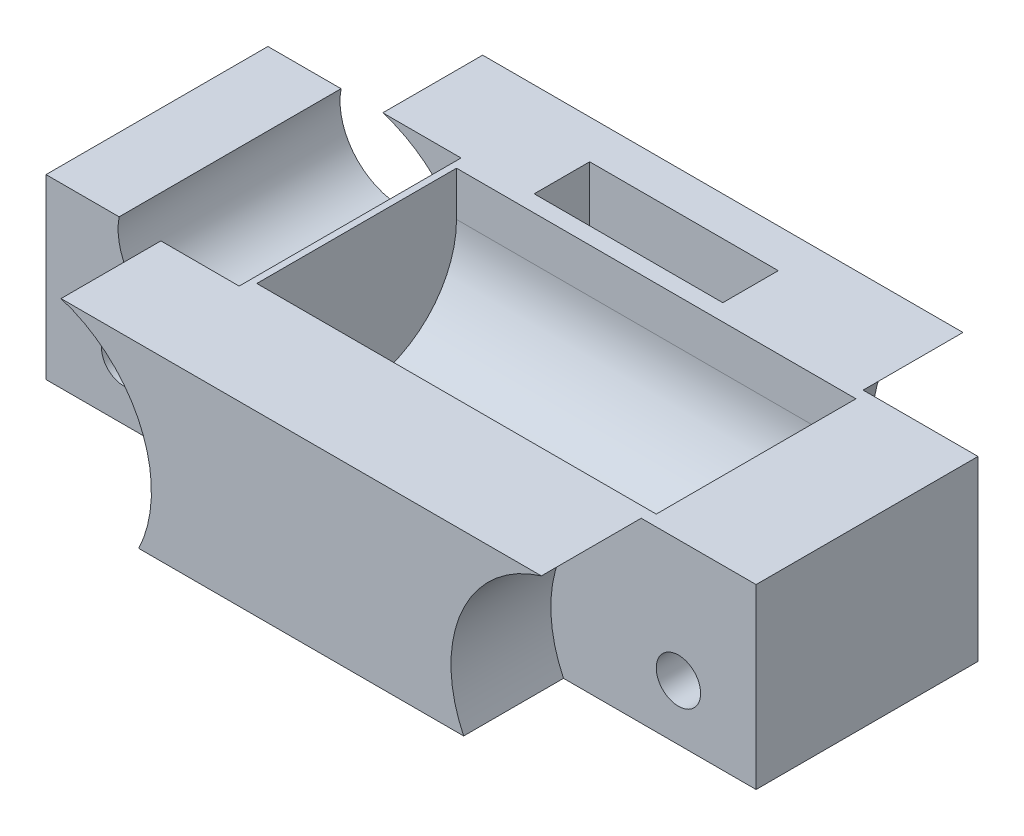
SolidWorks part; units mm, degrees
ref_plane "Front Plane" through (0, 0, 0) normal (0, 0, 1) x (1, 0, 0)
ref_plane "Top Plane" through (0, 0, 0) normal (0, 1, 0) x (1, 0, 0)
ref_plane "Right Plane" through (0, 0, 0) normal (1, 0, 0) x (0, 0, -1)
sketch "Sketch1" plane through (0, 0, 0) normal (0, 1, 0) x (1, 0, 0)
  line L1 (-32, 19) -> (32, 19)
  line L2 (-32, 19) -> (-32, -19)
  line L3 (-32, -19) -> (32, -19)
  line L4 (32, 19) -> (32, -19)
  line L5 (-32, 19) -> (32, -19) construction
  line L6 (-32, -19) -> (32, 19) construction
  point P0 (0, 0)
  dimension "D1" = 64
  dimension "D2" = 38
extrude "Boss-Extrude1" add sketch "Sketch1" along normal blind 16
sketch "Sketch2" plane through (0, 0, 0) normal (0, 0, 1) x (1, 0, 0)
  point P0 (-25, 5)
  point P1 (25, 5)
  dimension "D1" = 50
  dimension "D2" = 25
  dimension "D3" = 5
sketch "Sketch3" plane through (0, 0, 0) normal (0, 0, 1) x (1, 0, 0)
  line L0 (25, 16.5) -> (36.5, 16.5)
  line L1 (36.5, 16.5) -> (36.5, 5)
  line L2 (36.5, 5) -> (36.5, -6.5)
  line L3 (36.5, -6.5) -> (25, -6.5)
  line L4 (-25, -6.5) -> (-36.5, -6.5)
  line L5 (-36.5, -6.5) -> (-36.5, 16.5)
  line L6 (-36.5, 16.5) -> (-25, 16.5)
  circle A0 centre (-25, 5) radius 11.5
  circle A1 centre (25, 5) radius 11.5
  dimension "D1" = 23
extrude "Cut-Extrude2" cut sketch "Sketch3" along normal blind 10 from offset 10 contours A1 L3 L2 | A1 | A1 L1 L0 | A0 | A0 L5 L4 | A0 L6 L5 region at (33.9313, 13.9313, 0) region at (25, 5, 0) region at (33.9313, -3.9313, 0) region at (-25, 5, 0) region at (-33.9313, -3.9313, 0) region at (-33.9313, 13.9313, 0)
mirror "Mirror1" about plane through (0, 0, 0) normal (0, 0, 1) of "Cut-Extrude2"
sketch "Sketch5" plane through (0, 0, 0) normal (0, 0, 1) x (1, 0, 0)
  circle A0 centre (25, 5) radius 2
  circle A1 centre (-25, 5) radius 2
  dimension "D1" = 4
extrude "Cut-Extrude3" cut sketch "Sketch5" against normal through all both and the other way through all
sketch "Sketch4" plane through (0, 0, 0) normal (1, 0, 0) x (0, 0, -1)
  line L0 (-9, 12) -> (-9, 23.0528)
  line L1 (-9, 23.0528) -> (9, 23.0528)
  line L2 (9, 23.0528) -> (9, 12)
  circle A0 centre (0, 12) radius 9
  dimension "D1" = 18
  dimension "D2" = 12
extrude "Battery" add sketch "Sketch4" along normal blind 22 and the other way blind 14 separate body contours A0 | A0 L2 L1 L0 region at (0, 17.5264, 8.7888) region at (0, 12, 0)
combine bodies "Combine1" operation type subtract main body 106 bodies to subtract 104
sketch "Sketch6" plane through (0, 0, 0) normal (0, 1, 0) x (1, 0, 0)
  line L1 (8.5, 10.5) -> (-8.5, 10.5)
  line L2 (8.5, 10.5) -> (8.5, 15.5)
  line L3 (8.5, 15.5) -> (-8.5, 15.5)
  line L4 (-8.5, 10.5) -> (-8.5, 15.5)
  line L5 (8.5, 10.5) -> (-8.5, 15.5) construction
  line L6 (8.5, 15.5) -> (-8.5, 10.5) construction
  point P0 (0, 13)
  point P5 (0, 0)
  dimension "D1" = 17
  dimension "D2" = 5
  dimension "D3" = 13
extrude "Cut-Extrude4" cut sketch "Sketch6" along normal up to next from offset 3
sketch "Sketch7" plane through (0, 0, 0) normal (0, -1, 0) x (1, 0, 0)
  line L1 (6, -17) -> (-6, -17)
  line L2 (6, -17) -> (6, -9)
  line L3 (6, -9) -> (-6, -9)
  line L4 (-6, -17) -> (-6, -9)
  line L5 (6, -17) -> (-6, -9) construction
  line L6 (6, -9) -> (-6, -17) construction
  point P0 (0, -13)
  dimension "D1" = 12
  dimension "D2" = 8
extrude "Cut-Extrude5" cut sketch "Sketch7" against normal blind 3
fillet "Fillet1" radius 1.5 2 edges at (0, 3, -17) (0, 3, -9)
sketch "Sketch8" plane through (0, 0, 0) normal (0, 0, 1) x (1, 0, 0)
  circle A0 centre (-20, 15) radius 5.5
  dimension "D1" = 11
  dimension "D2" = 20
  dimension "D3" = 15
extrude "Cut-Extrude6" cut sketch "Sketch8" against normal mid plane 20
